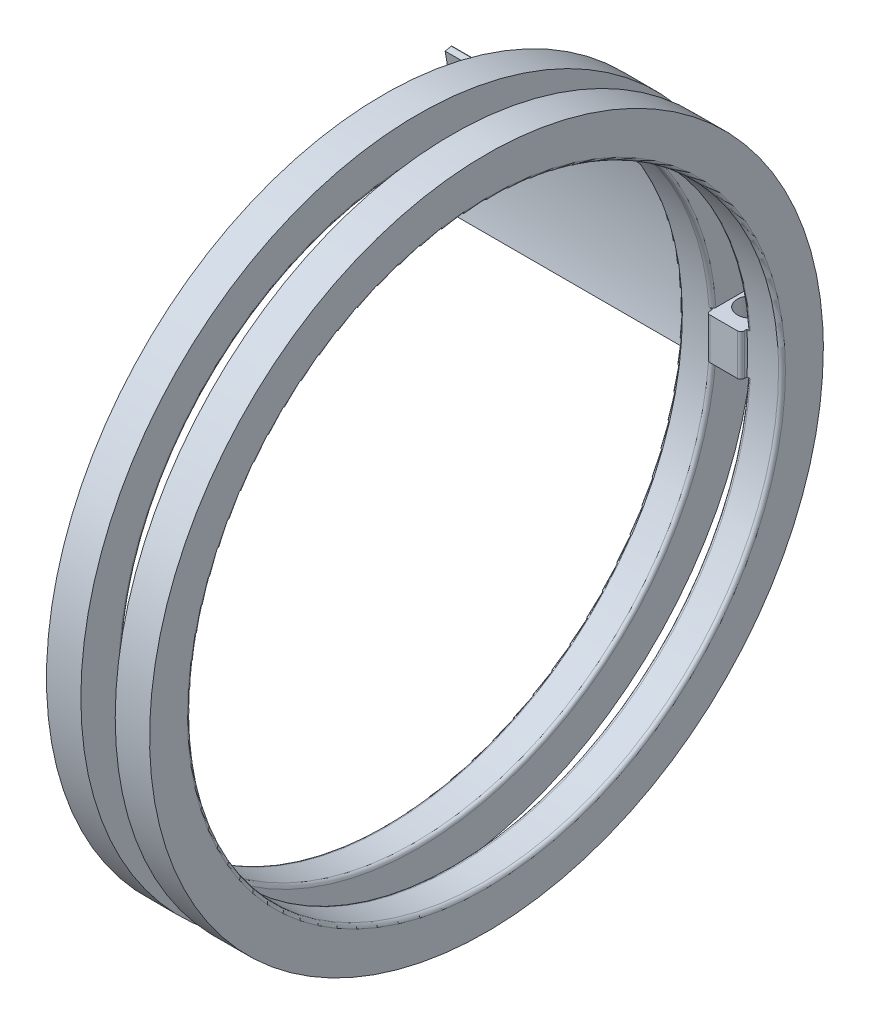
SolidWorks part; units mm, degrees
ref_plane "Front Plane" through (0, 0, 0) normal (0, 0, 1) x (1, 0, 0)
ref_plane "Top Plane" through (0, 0, 0) normal (0, 1, 0) x (1, 0, 0)
ref_plane "Right Plane" through (0, 0, 0) normal (1, 0, 0) x (0, 0, -1)
sketch "airflap" plane through (0, 0, 0) normal (1, 0, 0) x (0, 0, -1)
  line L0 (0, 0) -> (0, 50) construction
  line L1 (0, 0) -> (0, -50) construction
  line L2 (49.9696, 10.2) -> (48.9898, 10)
  line L3 (-48.9898, -10) -> (48.9898, -10) construction
  line L4 (-48.9898, -10) -> (-48.9898, 10) construction
  line L5 (-48.9898, 10) -> (48.9898, 10) construction
  line L6 (48.9898, -10) -> (48.9898, 10) construction
  line L7 (-48.9898, -10) -> (48.9898, 10) construction
  line L8 (-48.9898, 10) -> (48.9898, -10) construction
  line L9 (48.9898, -10) -> (49.9696, -10.2)
  arc A0 (48.9898, 10) -> (48.9898, -10) centre (0, 0) cw
  arc A1 (49.9696, 10.2) -> (49.9696, -10.2) centre (0, 0) cw
  dimension "D2" = 20
  dimension "D3" = 50
  dimension "D4" = 51
  dimension "D1" = 50
extrude "Boss-Extrude1" add sketch "airflap" along normal blind 50
fillet "Fillet3" radius 0.1 5 edges at (50, 10.1, -49.4797) (50, -10.1, -49.4797) (25, -10.2, -49.9696) (25, 10.2, -49.9696) (50, 0, -51)
ref_plane "hinge sketch" through (50, 0, 0) normal (1, 0, 0) x (0, 0, -1)
sketch "inner-hinge" plane through (50, 0, 0) normal (1, 0, 0) x (0, 0, -1)
  line L0 (49.0097, 9.902) -> (49.0097, -9.902) construction
  line L1 (49.0097, 0) -> (50, 0) construction
  line L2 (49.0097, 3) -> (42.0097, 3)
  line L4 (49.0097, -3) -> (42.0097, -3)
  line L5 (42.0097, 3) -> (42.0097, -3)
  line L6 (49.0097, 3) -> (49.9099, 3)
  line L8 (49.0097, -3) -> (49.9099, -3)
  line L9 (49.0097, 0) -> (42.0097, 0) construction
  arc A0 (49.0097, -9.902) -> (49.0097, 9.902) centre (0, 0) ccw construction
  arc A1 (49.9099, 3) -> (49.9099, -3) centre (0, 0) cw
  point P21 (43, 0)
  dimension "D3" = 7
  dimension "D1" = 6
  dimension "D2" = 42.0097
  dimension "D4" = 0.9903
  dimension "D5" = 0.9903
extrude "Boss-Extrude2" add sketch "inner-hinge" against normal blind 5 separate body
ref_plane "inner-screw hinge" through (0, 0, 0) normal (0, 1, 0) x (1, 0, 0)
sketch "cutout-hinge" plane through (0, 0, 0) normal (0, 1, 0) x (1, 0, 0)
  line L0 (47.5, 42.0097) -> (47.5, 50) construction
  line L1 (45, 42.0097) -> (50, 42.0097) construction
  line L2 (45, 42.0097) -> (50, 42.0097) construction
  circle A0 centre (47.5, 46.0048) radius 2
  point P6 (47.5, 51.0097)
  point P7 (0, 0)
  point P8 (47.5, 53.8299)
  point P10 (0, 0)
  dimension "D1" = 4
  dimension "D2" = 7.9903
  dimension "D3" = 3.9952
extrude "Cut-Extrude1" cut sketch "cutout-hinge" against normal through all both and the other way through all
fillet "Fillet4" radius 0.5 2 edges at (50, 0, -42.0097) (45, 0, -42.0097)
sketch "set ring" plane through (50, 0, 0) normal (1, 0, 0) x (0, 0, -1)
  circle A0 centre (0, 0) radius 49.0097
  circle A1 centre (0, 0) radius 43
extrude "setring" add sketch "set ring" along normal blind 5
ref_plane "mirrorplane" through (47.5, 0, 0) normal (1, 0, 0) x (0, 0, -1)
mirror "Mirror1" about plane through (47.5, 0, 0) normal (1, 0, 0) of "setring"
fillet "Fillet5" radius 0.5 4 edges at (40, 0, -43) (45, 0, 43) (50, 0, 43) (55, 0, -43)
equation "\"D3@cutout-hinge\" = \"D2@cutout-hinge\" / 2"
equation "\"D4@inner-hinge\"=\"D5@inner-hinge\""
